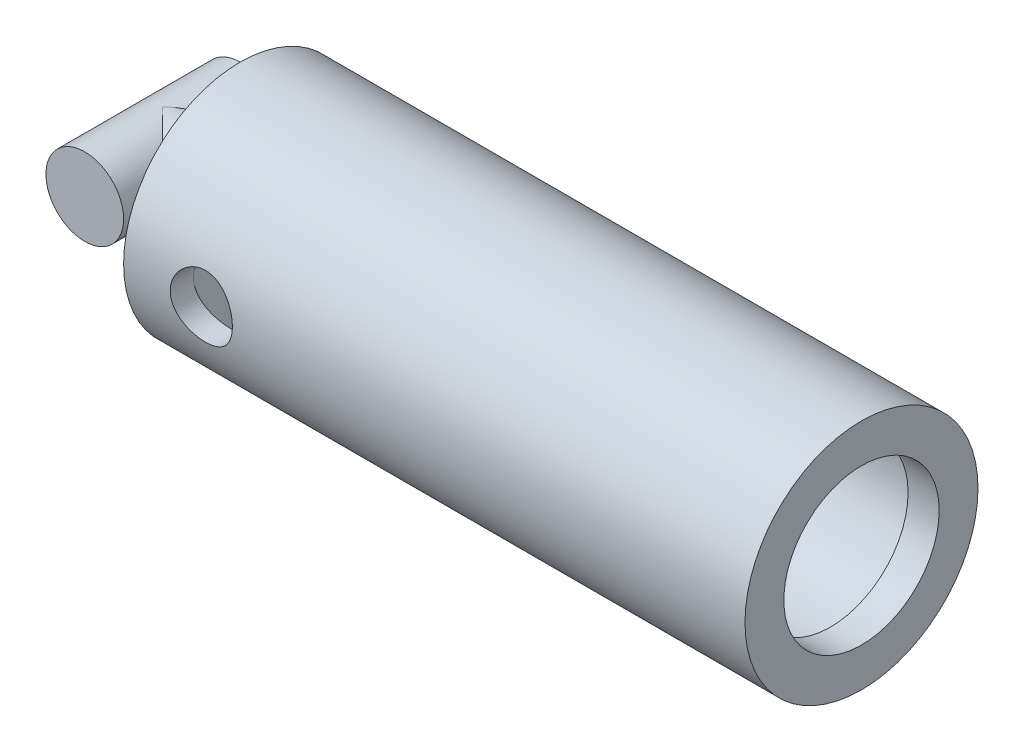
SolidWorks part; units mm, degrees
ref_plane "Front Plane" through (0, 0, 0) normal (0, 0, 1) x (1, 0, 0)
ref_plane "Top Plane" through (0, 0, 0) normal (0, 1, 0) x (1, 0, 0)
ref_plane "Right Plane" through (0, 0, 0) normal (1, 0, 0) x (0, 0, -1)
sketch "Sketch1" plane through (0, 0, 0) normal (1, 0, 0) x (0, 0, -1)
  circle A0 centre (0, 0) radius 7.5
  dimension "D1" = 15
extrude "Boss-Extrude1" add sketch "Sketch1" along normal blind 40
sketch "Sketch2" plane through (40, 0, 0) normal (1, 0, 0) x (0, 0, -1)
  circle A0 centre (0, 0) radius 5
  dimension "D1" = 10
extrude "Cut-Extrude1" cut sketch "Sketch2" against normal blind 2
sketch "Sketch3" plane through (38, 0, 0) normal (1, 0, 0) x (0, 0, -1)
  circle A0 centre (0, 0) radius 6
  dimension "D1" = 12
extrude "Cut-Extrude2" cut sketch "Sketch3" against normal blind 35
sketch "Sketch4" plane through (0, 0, 0) normal (-1, 0, 0) x (0, 0, 1)
  circle A0 centre (0, 0) radius 2.5
  dimension "D1" = 5
extrude "Boss-Extrude4" add sketch "Sketch4" along normal blind 5
sketch "Sketch6" plane through (0, 0, 0) normal (0, 0, 1) x (1, 0, 0)
  line L0 (-5, 2.5) -> (-5, -2.5) construction
  circle A0 centre (-5, 0) radius 2.5
extrude "Boss-Extrude5" add sketch "Sketch6" along normal blind 5 and the other way blind 5
sketch3d "3DSketch1"
  line L0 (40, -5, 0) -> (38, -5, 0) construction
  circle A0 centre (40, 0, 0) radius 5 construction
  circle A1 centre (38, 0, 0) radius 5 construction
  point P4 (45, 0, 0)
  point P7 (33, 0, 0)
sketch3d "3DSketch3"
  line L0 (0, 0, -7.5) -> (5, 0, -7.5) construction
  circle A0 centre (5, 0, -7.5) radius 2
  point P4 (5, 0, -5.5)
  dimension "D3" = 4
  dimension "D1" = 7.5
  dimension "D2" = 5
extrude "Cut-Extrude3" cut sketch "3DSketch3" along direction (0, 0, 1) on the side against the normal through all
